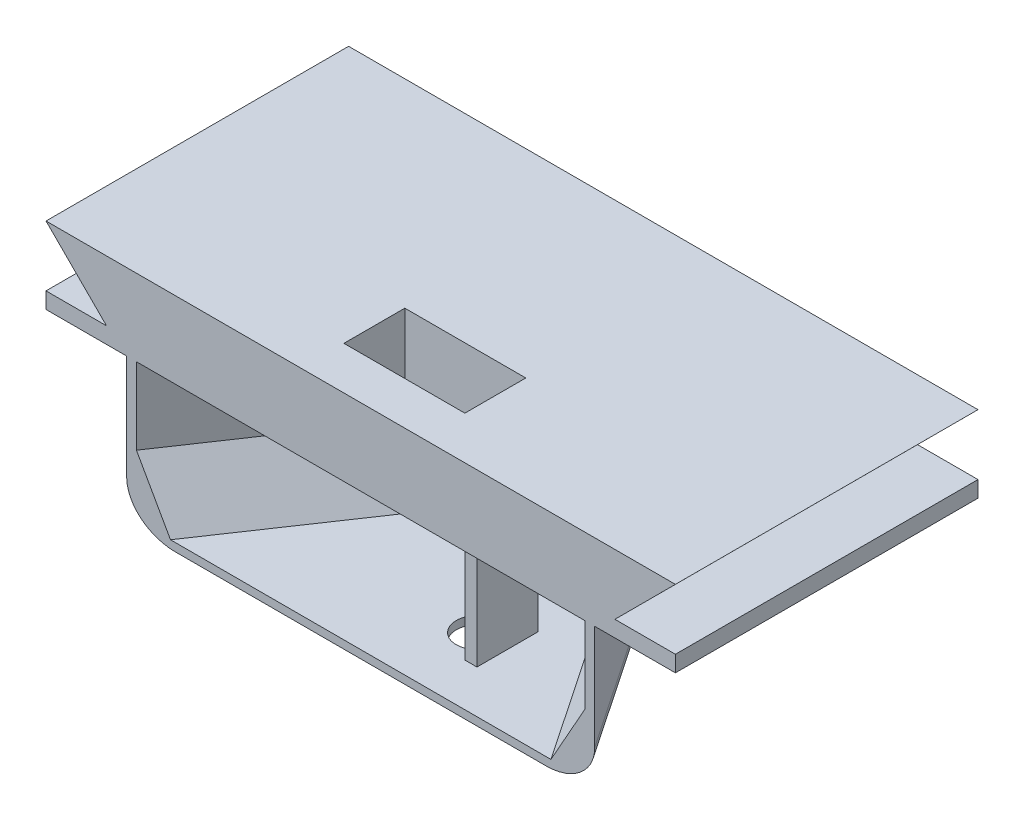
SolidWorks part; units mm, degrees
other "Camera1"
ref_plane "Front Plane" through (0, 0, 0) normal (0, 0, 1) x (1, 0, 0)
ref_plane "Top Plane" through (0, 0, 0) normal (0, 1, 0) x (1, 0, 0)
ref_plane "Right Plane" through (0, 0, 0) normal (1, 0, 0) x (0, 0, -1)
sketch "Sketch1" plane through (0, 0, 0) normal (0, 1, 0) x (1, 0, 0)
  line L0 (0, 0) -> (-116, 0)
  line L1 (-116, 0) -> (-75.5008, 60)
  line L2 (-75.5008, 60) -> (-40.5008, 60)
  line L3 (-40.5008, 60) -> (0, 0)
  dimension "D1" = 60
  dimension "D2" = 116
  dimension "D3" = 35
  dimension "D5" = 72.39
  dimension "D6" = 72.3891
extrude "Boss-Extrude1" add sketch "Sketch1" against normal blind 40
shell "Shell1" thickness 2 removed face at (-58, -20, 0)
chamfer "Chamfer3" distance 15 angle 25 2 edges at (-94.0124, -38, -29) (-21.9884, -38, -29) first distance on face at (-94.0124, -20, -29) first distance on face at (-21.9884, -20, -29)
fillet "Fillet1" radius 10 2 edges at (-20.2504, -40, -30) (-95.7504, -40, -30)
fillet "Fillet2" radius 5 5 edges at (-40.5008, -15, -60) (-44.0345, -37.0711, -60) (-75.5008, -15, -60) (-71.9671, -37.0711, -60) (-58.0008, -40, -60)
sketch "Sketch12" plane through (0, -40, 0) normal (0, -1, 0) x (-1, 0, 0)
  circle A0 centre (47.2011, 18.0841) radius 5.2
sketch "Sketch13" plane through (0, -2, 0) normal (0, -1, 0) x (1, 0, 0)
  line L1 (-39.8423, -25.7584) -> (-42.8423, -25.7584)
  line L2 (-39.8423, -25.7584) -> (-39.8423, -10.6584)
  line L3 (-39.8423, -10.6584) -> (-42.8423, -10.6584)
  line L4 (-42.8423, -25.7584) -> (-42.8423, -10.6584)
  dimension "D1" = 3
extrude "Boss-Extrude3" add sketch "Sketch13" along normal blind 36
extrude "Cut-Extrude12" cut sketch "Sketch12" against normal blind 9
sketch "Sketch15" plane through (0, 0, 0) normal (0, 1, 0) x (1, 0, 0)
  line L8 (-136, 75) -> (20, 75)
  line L9 (20, 0) -> (20, 75)
  line L10 (20, 0) -> (-136, 0)
  line L11 (-136, 0) -> (-136, 75)
extrude "Boss-Extrude7" add sketch "Sketch15" along normal blind 15
sketch "Sketch16" plane through (0, 0, 0) normal (0, 0, 1) x (1, 0, 0)
  line L8 (20, 15) -> (20, 0)
  line L9 (20, 0) -> (5.0045, 0)
  line L10 (0, 0) -> (20, 0) construction
  line L11 (5.0045, 0) -> (20, 15)
extrude "Cut-Extrude14" cut sketch "Sketch16" against normal blind 75
sketch "Sketch17" plane through (0, 0, 0) normal (0, 0, 1) x (1, 0, 0)
  line L0 (-136, 15) -> (-136, 0)
  line L1 (-136, 0) -> (-121.0045, 0)
  line L2 (-136, 0) -> (-116, 0) construction
  line L3 (-121.0045, 0) -> (-136, 15)
extrude "Cut-Extrude15" cut sketch "Sketch17" against normal blind 75
sketch "Sketch18" plane through (0, 0, 0) normal (0, -1, 0) x (1, 0, 0)
  line L0 (-116, 0) -> (-121.0045, 0)
  line L1 (-121.0045, 0) -> (-136.0045, 0)
  line L2 (-136.0045, 0) -> (-136.0045, -75)
  line L3 (-136.0045, -75) -> (-121.0045, -75)
  line L5 (20.0045, -75) -> (20.0045, 0)
  line L6 (20.0045, 0) -> (-116, 0)
  line L7 (20.0045, -75) -> (5.0045, -75)
  line L8 (-121.0045, -75) -> (5.0045, -75)
extrude "Boss-Extrude8" add sketch "Sketch18" along normal blind 4 contours L8 L7 L5 L6 L0 L1 L2 L3
sketch "Sketch20" plane through (0, -4, 0) normal (0, -1, 0) x (-1, 0, 0)
  line L1 (42.8423, 25.7584) -> (72.8207, 25.7584)
  line L2 (42.8423, 25.7584) -> (42.8423, 10.6584)
  line L3 (42.8423, 10.6584) -> (72.8207, 10.6584)
  line L4 (72.8207, 25.7584) -> (72.8207, 10.6584)
extrude "Cut-Extrude17" cut sketch "Sketch20" against normal blind 39 contours L2 L1 L4 L3
sketch "Sketch26" plane through (-42.8423, 0, 0) normal (-1, 0, 0) x (0, 0, 1)
  line L6 (-10.6584, -38) -> (-18.2084, -38)
  line L7 (-10.6584, -38) -> (-10.6584, -10.7935)
  line L8 (-10.6584, -10.7935) -> (-18.2084, -10.7935)
  line L9 (-18.2084, -38) -> (-18.2084, -10.7935)
sketch "Sketch29" plane through (-42.8423, 0, 0) normal (-1, 0, 0) x (0, 0, 1)
  circle A0 centre (-18.2084, -10.7935) radius 2.1
extrude "Cut-Extrude22" cut sketch "Sketch29" against normal blind 10 contours A0
sketch "Sketch32" plane through (0, 0, -58) normal (0, 0, 1) x (1, 0, 0)
sketch "Sketch33" plane through (0, 0, -58) normal (0, 0, 1) x (1, 0, 0)
sketch "Sketch34" plane through (0, 0, -58) normal (0, 0, 1) x (1, 0, 0)
  line L0 (-74.4378, -23) -> (-74.4378, -4) construction
  line L1 (-53.7528, -25.65) -> (-62.2528, -25.65)
  line L2 (-53.7528, -25.65) -> (-53.7528, -17.15)
  line L3 (-53.7528, -17.15) -> (-62.2528, -17.15)
  line L4 (-62.2528, -25.65) -> (-62.2528, -17.15)
  line L10 (-41.5637, -4) -> (-74.4378, -4) construction
  circle A0 centre (-68.5028, -21.5) radius 1.1
  circle A1 centre (-68.5028, -9) radius 1.1
  point P8 (-63.4741, -10.7398)
  dimension "D5" = 6.25
  dimension "D6" = 17.5
  dimension "D7" = 6.25
  dimension "D8" = 5
  dimension "D1" = 12.185
  dimension "D2" = 8.5
  dimension "D3" = 8.5
  dimension "D4" = 13.15
extrude "Cut-Extrude23" cut sketch "Sketch34" against normal blind 10
sketch "Sketch35" plane through (0, 0, -58) normal (0, 0, 1) x (1, 0, 0)
  line L0 (-53.7528, -25.65) -> (-53.7528, -17.15) construction
  line L1 (-41.5637, -4) -> (-74.4378, -4) construction
  circle A0 centre (-47.5028, -21.5) radius 1.1
  circle A1 centre (-47.5028, -9) radius 1.1
  dimension "D1" = 6.25
  dimension "D2" = 17.5
  dimension "D3" = 6.25
  dimension "D4" = 5
extrude "Cut-Extrude24" cut sketch "Sketch35" against normal blind 10
